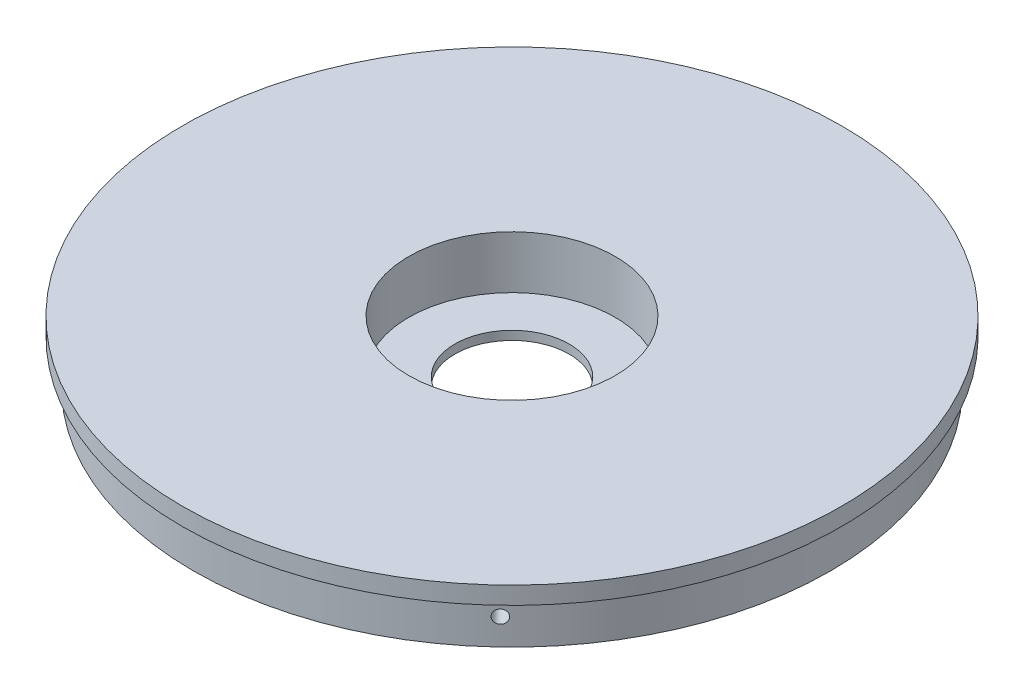
SolidWorks part; units mm, degrees
ref_plane "Płaszczyzna przednia" through (0, 0, 0) normal (0, 0, 1) x (1, 0, 0)
ref_plane "Płaszczyzna górna" through (0, 0, 0) normal (0, 1, 0) x (1, 0, 0)
ref_plane "Płaszczyzna prawa" through (0, 0, 0) normal (1, 0, 0) x (0, 0, -1)
sketch "Szkic4" plane through (0, 0, 0) normal (0, 1, 0) x (1, 0, 0)
  circle A0 centre (0, 0) radius 75
extrude "Dodanie-wyciągnięcie2" add sketch "Szkic4" along normal blind 14
sketch "Szkic5" plane through (0, 14, 0) normal (0, 1, 0) x (1, 0, 0)
  circle A0 centre (0, 0) radius 23.5
extrude "Wytnij-wyciągnięcie3" cut sketch "Szkic5" against normal blind 12
sketch "Szkic6" plane through (0, 2, 0) normal (0, 1, 0) x (1, 0, 0)
  circle A0 centre (0, 0) radius 13
  dimension "D1" = 26
extrude "Wytnij-wyciągnięcie4" cut sketch "Szkic6" against normal blind 12
sketch "Szkic7" plane through (0, 0, 0) normal (0, -1, 0) x (1, 0, 0)
  circle A0 centre (0, 0) radius 75
  circle A1 centre (0, 0) radius 72.5
  circle A2 centre (0, 0) radius 75 construction
  dimension "D1" = 2.5
extrude "Wytnij-wyciągnięcie5" cut sketch "Szkic7" against normal blind 10
sketch "Szkic8" plane through (0, 0, 0) normal (0, -1, 0) x (-1, 0, 0)
  circle A0 centre (21.8998, -20.7951) radius 1.5
  circle A1 centre (-27.411, 26.0284) radius 1.5
extrude "Wytnij-wyciągnięcie6" cut sketch "Szkic8" against normal blind 6
sketch "Szkic9" plane through (0, 0, 0) normal (0, -1, 0) x (-1, 0, 0)
  line L0 (-27.411, 26.0284) -> (21.8998, -20.7951) construction
ref_plane "Płaszczyzna1" through (52.5741, 0, -49.9221) normal (-0.7252, 0, 0.6886) x (0.6886, 0, 0.7252)
sketch "Szkic10" plane through (52.5741, 0, -49.9221) normal (-0.7252, 0, 0.6886) x (0.6886, 0, 0.7252)
  line L0 (-72.5, 10) -> (72.5, 10) construction
  circle A0 centre (0, 6) radius 1.5
  dimension "D1" = 3
  dimension "D2" = 4
extrude "Wytnij-wyciągnięcie7" cut sketch "Szkic10" along normal blind 6
pattern_circular "Szyk kołowy1" count 4 over 360 about axis through (0, 10, 0) along (0, -1, 0) of "Wytnij-wyciągnięcie7" reverse direction yes
